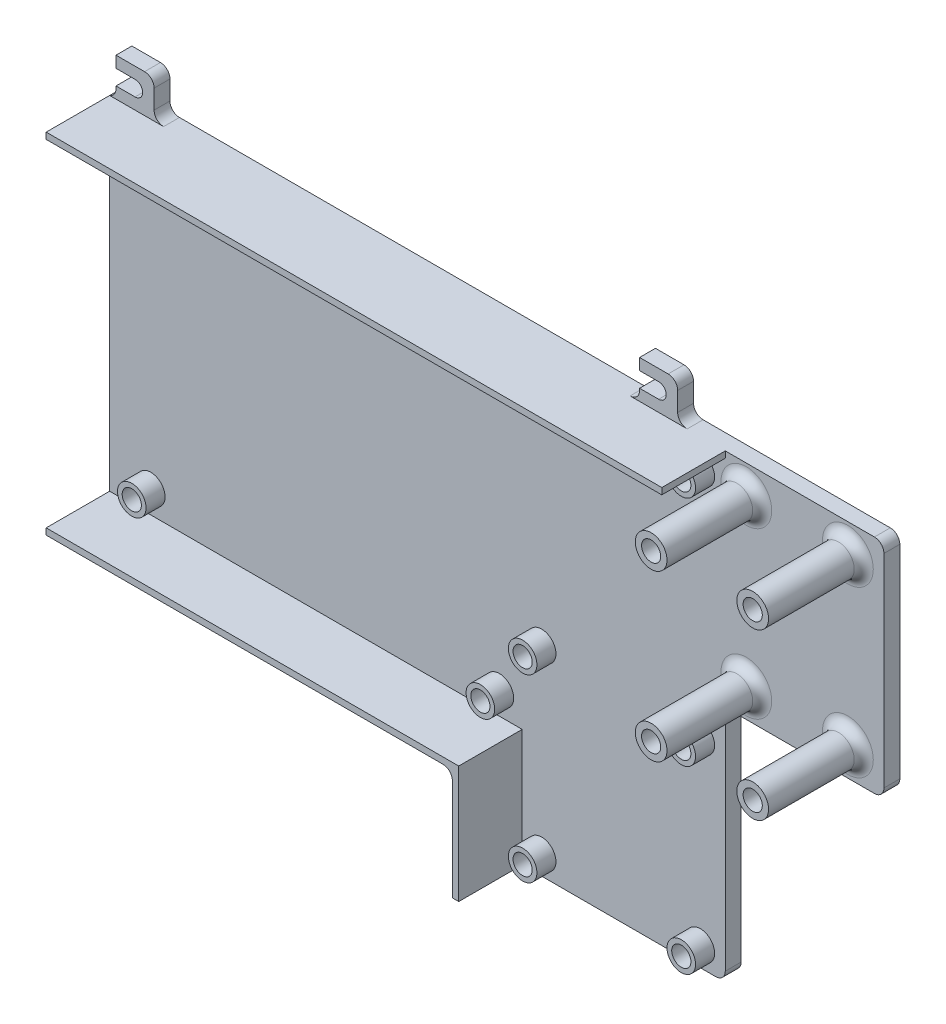
SolidWorks part; units mm, degrees
material "ABS"
ref_plane "X-Y Datum" through (0, 0, 0) normal (0, 0, 1) x (1, 0, 0)
ref_plane "X-Z Datum" through (0, 0, 0) normal (0, 1, 0) x (1, 0, 0)
ref_plane "Y-Z Datum" through (0, 0, 0) normal (1, 0, 0) x (0, 0, -1)
sketch "Sketch1" plane through (0, 0, 0) normal (0, 0, 1) x (1, 0, 0)
  line L1 (-167.3248, 270.3744) -> (-39.3248, 270.3744)
  line L2 (-167.3248, 270.3744) -> (-167.3248, 160.3744)
  line L3 (-167.3248, 160.3744) -> (-39.3248, 160.3744)
  line L4 (-39.3248, 270.3744) -> (-39.3248, 160.3744)
  line L5 (-39.3248, 270.3744) -> (26.6752, 270.3744)
  line L6 (-39.3248, 270.3744) -> (-39.3248, 125.3744)
  line L7 (-39.3248, 125.3744) -> (26.6752, 125.3744)
  line L8 (26.6752, 270.3744) -> (26.6752, 125.3744)
  line L10 (26.6752, 125.3744) -> (26.6752, 195.3744)
  line L13 (26.6752, 270.3744) -> (76.6752, 270.3744)
  line L14 (26.6752, 270.3744) -> (26.6752, 200.3744)
  line L15 (26.6752, 200.3744) -> (76.6752, 200.3744)
  line L16 (76.6752, 270.3744) -> (76.6752, 200.3744)
  dimension "D1" = 110
  dimension "D2" = 128
  dimension "D3" = 66
  dimension "D4" = 145
  dimension "D7" = 70
  dimension "D8" = 50
extrude "Boss-Extrude1" add sketch "Sketch1" along normal blind 5 contours L4 L1 L2 L3 | L8 L5 L4 L6 L7 | L8 region at (-103.3248, 215.3744, 0) region at (-6.3248, 197.8744, 0) region at (51.6752, 235.3744, 0)
sketch "Sketch2" plane through (0, 0, 5) normal (0, 0, 1) x (1, 0, 0)
  circle A0 centre (-44.4998, 262.4914) radius 3.025
  circle A1 centre (-154.3548, 262.4914) radius 3.025
  circle A2 centre (-154.3548, 262.4914) radius 4.5
  circle A3 centre (-44.4998, 262.4914) radius 4.5
  circle A4 centre (-44.4998, 169.5274) radius 3.025
  circle A5 centre (-44.4998, 169.5274) radius 4.5
  circle A6 centre (-154.3548, 169.5274) radius 4.5
  circle A7 centre (-154.3548, 169.5274) radius 3.025
  circle A8 centre (-31.1818, 131.5554) radius 4.5
  circle A9 centre (-31.1818, 131.5554) radius 3.025
  circle A10 centre (18.8182, 131.5554) radius 3.025
  circle A11 centre (18.8182, 131.5554) radius 4.5
  circle A12 centre (18.8182, 188.3054) radius 3.025
  circle A13 centre (18.8182, 188.3054) radius 4.5
  circle A14 centre (-31.1818, 188.3054) radius 4.5
  circle A15 centre (-31.1818, 188.3054) radius 3.025
  circle A16 centre (-31.1818, 261.5554) radius 3.025
  circle A17 centre (-31.1818, 261.5554) radius 4.5
  circle A18 centre (18.8182, 261.5554) radius 4.5
  circle A19 centre (18.8182, 261.5554) radius 3.025
  point P0 (-154.3548, 262.4914)
  point P1 (-44.4998, 262.4914)
  point P3 (-44.4998, 169.5274)
  point P5 (-154.3548, 169.5274)
  point P7 (18.8182, 261.5554)
  point P9 (-31.1818, 261.5554)
  point P11 (-31.1818, 188.3054)
  point P13 (-31.1818, 131.5554)
  point P15 (18.8182, 131.5554)
  point P17 (18.8182, 188.3054)
  dimension "D1" = 6.05
  dimension "D2" = 9
extrude "Boss-Extrude2" add sketch "Sketch2" along normal blind 6
sketch "Sketch3" plane through (0, 0, 5) normal (0, 0, 1) x (1, 0, 0)
  line L0 (26.6752, 200.3744) -> (26.6752, 125.3744) construction
  line L1 (-167.3248, 270.3744) -> (26.6752, 270.3744)
  line L2 (-167.3248, 270.3744) -> (-167.3248, 268.3744)
  line L3 (-167.3248, 268.3744) -> (26.6752, 268.3744)
  line L4 (26.6752, 270.3744) -> (26.6752, 268.3744)
  line L6 (-167.3248, 160.3744) -> (-39.3248, 160.3744)
  line L7 (-167.3248, 160.3744) -> (-167.3248, 162.3744)
  line L8 (-167.3248, 162.3744) -> (-39.3248, 162.3744)
  line L9 (-39.3248, 160.3744) -> (-39.3248, 162.3744)
  line L10 (-39.3248, 125.3744) -> (-37.3248, 125.3744)
  line L11 (-39.3248, 125.3744) -> (-39.3248, 162.3744)
  line L12 (-39.3248, 162.3744) -> (-37.3248, 162.3744)
  line L13 (-37.3248, 125.3744) -> (-37.3248, 162.3744)
  line M14 (-167.3248, 160.3744) -> (-39.3248, 160.3744)
  line M15 (-39.3248, 160.3744) -> (-39.3248, 125.3744)
  line M19 (26.6752, 125.3744) -> (26.6752, 200.3744)
  line M20 (76.6752, 270.3744) -> (-167.3248, 270.3744)
  line M21 (-167.3248, 270.3744) -> (-167.3248, 160.3744)
  dimension "D1" = 2
  dimension "D2" = 2
  dimension "D3" = 2
extrude "Boss-Extrude3" add sketch "Sketch3" along normal blind 20 contours L13 L12 L9 M15 | L9 L8 M14 M21 | L3 M21 M19 M20 region at (-103.3248, 161.3744, 5) region at (-70.3248, 269.3744, 5) region at (-38.3248, 143.8744, 5)
sketch "Sketch6" plane through (0, 0, 0) normal (0, 0, -1) x (-1, 0, 0)
  line L0 (167.3248, 160.3744) -> (39.3248, 160.3744) construction
  line L1 (137.3248, 160.3744) -> (125.3248, 160.3744)
  line L2 (137.3248, 160.3744) -> (137.3248, 148.3744)
  line L3 (137.3248, 148.3744) -> (125.3248, 148.3744)
  line L4 (125.3248, 160.3744) -> (125.3248, 148.3744)
  line L5 (-26.6752, 270.3744) -> (167.3248, 270.3744) construction
  line L6 (165.3248, 270.3744) -> (153.3248, 270.3744)
  line L7 (165.3248, 270.3744) -> (165.3248, 282.3744)
  line L8 (165.3248, 282.3744) -> (153.3248, 282.3744)
  line L9 (153.3248, 270.3744) -> (153.3248, 282.3744)
  line L11 (51.3248, 160.3744) -> (39.3248, 160.3744)
  line L12 (51.3248, 160.3744) -> (51.3248, 148.3744)
  line L13 (51.3248, 148.3744) -> (39.3248, 148.3744)
  line L14 (39.3248, 160.3744) -> (39.3248, 148.3744)
  line L15 (131.3248, 160.3744) -> (131.3248, 148.3744) construction
  line L16 (0.3248, 270.3744) -> (-11.6752, 270.3744)
  line L17 (0.3248, 270.3744) -> (0.3248, 282.3744)
  line L18 (0.3248, 282.3744) -> (-11.6752, 282.3744)
  line L19 (-11.6752, 270.3744) -> (-11.6752, 282.3744)
  line L20 (167.3248, 162.3744) -> (167.3248, 160.3744) construction
  line L21 (159.3248, 282.3744) -> (159.3248, 270.3744) construction
  line L22 (-5.6752, 282.3744) -> (-5.6752, 270.3744) construction
  line L23 (45.3248, 160.3744) -> (45.3248, 148.3744) construction
  line L24 (167.3248, 268.3744) -> (167.3248, 162.3744) construction
  line L27 (-26.6752, 200.3744) -> (-26.6752, 125.3744) construction
  line L29 (39.3248, 125.3744) -> (39.3248, 160.3744) construction
  circle A0 centre (131.3248, 154.3744) radius 2 construction
  circle A1 centre (45.3248, 154.3744) radius 2 construction
  circle A2 centre (-5.6752, 276.3744) radius 2 construction
  circle A3 centre (159.3248, 276.3744) radius 2 construction
  dimension "D1" = 4
  dimension "D2" = 12
  dimension "D3" = 12
  dimension "D4" = 30
  dimension "D5" = 2
  dimension "D6" = 15
extrude "Boss-Extrude5" add sketch "Sketch6" against normal blind 5
hole_wizard "M4 Clearance Hole1" positions "Sketch9" profile "Sketch8" hole size "M4" standard "ANSI Metric" end condition through all
sketch "Sketch9" plane through (0, 0, 5) normal (0, 0, 1) x (1, 0, 0)
  line L0 (-131.3248, 160.3744) -> (-131.3248, 148.3744) construction
  point P0 (-131.3248, 154.3744)
  point P4 (-159.3248, 276.3744)
  point P7 (5.6752, 276.3744)
  point P10 (-45.3248, 154.3744)
sketch "Sketch8" plane through (-131.3248, 154.3744, 5) normal (1, 0, 0) x (0, -1, 0)
  line L0 (0, 0) -> (0, 5)
  line L1 (0, 5) -> (2.4, 5)
  line L2 (2.4, 5) -> (2.4, 0)
  line L5 (2.4, 0) -> (0, 0)
  line L11 (0, -6.35) -> (0, 107.95) construction
  dimension "Thru Hole Dia." = 4.8
  dimension "Thru Hole Depth" = 5
sketch "Sketch10" plane through (0, 0, 5) normal (0, 0, 1) x (1, 0, 0)
  line L0 (-159.3248, 278.7744) -> (-165.3248, 278.7744)
  line L1 (-159.3248, 282.3744) -> (-159.3248, 270.3744) construction
  line L2 (-165.3248, 270.3744) -> (-165.3248, 282.3744) construction
  line L3 (-159.3248, 273.9744) -> (-165.3248, 273.9744)
  line L4 (-131.3248, 156.7744) -> (-137.3248, 156.7744)
  line L5 (-131.3248, 160.3744) -> (-131.3248, 148.3744) construction
  line L6 (-137.3248, 160.3744) -> (-137.3248, 148.3744) construction
  line L7 (-131.3248, 151.9744) -> (-137.3248, 151.9744)
  line L8 (-45.3248, 156.7744) -> (-51.3248, 156.7744)
  line L9 (-45.3248, 160.3744) -> (-45.3248, 148.3744) construction
  line L10 (-51.3248, 160.3744) -> (-51.3248, 148.3744) construction
  line L11 (-45.3248, 151.9744) -> (-51.3248, 151.9744)
  line L12 (5.6752, 278.7744) -> (-0.3248, 278.7744)
  line L13 (5.6752, 282.3744) -> (5.6752, 270.3744) construction
  line L14 (-0.3248, 270.3744) -> (-0.3248, 282.3744) construction
  line L15 (5.6752, 273.9744) -> (-0.3248, 273.9744)
  line L16 (-51.3248, 148.3744) -> (-51.3248, 160.3744) construction
  line L17 (-51.3248, 148.3744) -> (-51.3248, 160.3744)
  line L20 (-137.3248, 160.3744) -> (-137.3248, 148.3744)
  line L21 (-137.3248, 148.3744) -> (-125.3248, 148.3744)
  line L22 (-125.3248, 148.3744) -> (-125.3248, 160.3744)
  line L23 (-125.3248, 160.3744) -> (-137.3248, 160.3744)
  line L24 (-137.3248, 160.3744) -> (-137.3248, 148.3744)
  line L25 (-137.3248, 148.3744) -> (-125.3248, 148.3744)
  line L26 (-125.3248, 148.3744) -> (-125.3248, 160.3744)
  line L27 (-125.3248, 160.3744) -> (-137.3248, 160.3744)
  line L28 (-0.3248, 282.3744) -> (-0.3248, 270.3744)
  line L29 (-0.3248, 270.3744) -> (11.6752, 270.3744)
  line L30 (26.6752, 125.3744) -> (26.6752, 200.3744)
  line L34 (26.6752, 268.3744) -> (-167.3248, 268.3744)
  line L35 (-167.3248, 268.3744) -> (-167.3248, 162.3744)
  line L36 (-167.3248, 162.3744) -> (-37.3248, 162.3744)
  line L37 (-37.3248, 162.3744) -> (-37.3248, 125.3744)
  line L38 (26.6752, 200.3744) -> (76.6752, 200.3744)
  line L48 (26.6752, 268.3744) -> (-167.3248, 268.3744)
  line L49 (-167.3248, 268.3744) -> (-167.3248, 162.3744)
  line L50 (-167.3248, 162.3744) -> (-37.3248, 162.3744)
  line L51 (-37.3248, 162.3744) -> (-37.3248, 125.3744)
  line L58 (11.6752, 270.3744) -> (11.6752, 282.3744)
  line L59 (11.6752, 282.3744) -> (-0.3248, 282.3744)
  line L60 (-0.3248, 282.3744) -> (-0.3248, 270.3744)
  line L61 (-0.3248, 270.3744) -> (11.6752, 270.3744)
  line L62 (11.6752, 270.3744) -> (11.6752, 282.3744)
  line L63 (11.6752, 282.3744) -> (-0.3248, 282.3744)
  line L64 (-165.3248, 282.3744) -> (-165.3248, 270.3744)
  line L65 (-165.3248, 270.3744) -> (-153.3248, 270.3744)
  line L66 (-153.3248, 270.3744) -> (-153.3248, 282.3744)
  line L67 (-153.3248, 282.3744) -> (-165.3248, 282.3744)
  line L68 (-165.3248, 282.3744) -> (-165.3248, 270.3744)
  line L69 (-165.3248, 270.3744) -> (-153.3248, 270.3744)
  line L70 (-153.3248, 270.3744) -> (-153.3248, 282.3744)
  line L71 (-153.3248, 282.3744) -> (-165.3248, 282.3744)
  line L80 (26.6752, 200.3744) -> (76.6752, 200.3744)
  line L82 (76.6752, 200.3744) -> (76.6752, 270.3744)
  line L84 (76.6752, 200.3744) -> (76.6752, 270.3744)
  line L85 (76.6752, 270.3744) -> (26.6752, 270.3744)
  line L86 (76.6752, 270.3744) -> (26.6752, 270.3744)
  line L87 (26.6752, 270.3744) -> (26.6752, 268.3744)
  line L89 (-37.3248, 125.3744) -> (26.6752, 125.3744)
  line L90 (-37.3248, 125.3744) -> (26.6752, 125.3744)
  line L94 (26.6752, 270.3744) -> (26.6752, 268.3744)
  line L95 (26.6752, 125.3744) -> (26.6752, 200.3744)
  circle A0 centre (-159.3248, 276.3744) radius 2.4 construction
  circle A1 centre (-131.3248, 154.3744) radius 2.4 construction
  circle A2 centre (-45.3248, 154.3744) radius 2.4 construction
  circle A3 centre (5.6752, 276.3744) radius 2.4 construction
  circle A4 centre (-159.3248, 276.3744) radius 2.4
  circle A5 centre (5.6752, 276.3744) radius 2.4
  circle A10 centre (-45.3248, 154.3744) radius 2.4
  circle A11 centre (-131.3248, 154.3744) radius 2.4
  circle M29 centre (-131.3248, 154.3744) radius 2.4
  line M30 (-137.3248, 160.3744) -> (-137.3248, 148.3744)
  dimension "D1" = 0
  dimension "D2" = 0
  dimension "D3" = 0
  dimension "D4" = 0
extrude "Cut-Extrude1" cut sketch "Sketch10" against normal through all contours L7 L4 M29 M30 | A4 L0 L68 L3 | A5 L12 L60 L15 | A10 L8 L11 region at (-163.2324, 276.3744, 5) region at (-135.2324, 154.3744, 5) region at (-49.2324, 154.3744, 5) region at (1.7676, 276.3744, 5)
fillet "Fillet2" radius 3 11 edges at (-153.3248, 282.3744, 2.5) (-153.3248, 270.3744, 2.5) (-165.3248, 270.3744, 2.5) (-0.3248, 270.3744, 2.5) (11.6752, 270.3744, 2.5) (11.6752, 282.3744, 2.5) (-125.3248, 148.3744, 2.5) (-137.3248, 160.3744, 2.5) (-125.3248, 160.3744, 2.5) (-51.3248, 160.3744, 2.5) (-39.3248, 148.3744, 2.5)
fillet "Fillet3" radius 3 5 edges at (-39.3248, 160.3744, 15) (26.6752, 200.3744, 2.5) (76.6752, 270.3744, 2.5) (76.6752, 200.3744, 2.5) (26.6752, 125.3744, 2.5)
sketch "Sketch11" plane through (0, 0, 5) normal (0, 0, 1) x (1, 0, 0)
  circle A0 centre (33.3182, 261.3744) radius 5
  circle A1 centre (65.3182, 261.3744) radius 3.025
  circle A2 centre (65.3182, 209.3744) radius 3.025
  circle A3 centre (33.3182, 209.3744) radius 3.025
  circle A4 centre (33.3182, 261.3744) radius 3.025
  circle A5 centre (65.3182, 261.3744) radius 5
  circle A6 centre (65.3182, 209.3744) radius 5
  circle A7 centre (33.3182, 209.3744) radius 5
  dimension "D1" = 6.05
  dimension "D2" = 10
extrude "Boss-Extrude6" add sketch "Sketch11" along normal blind 30
fillet "Fillet4" radius 3 4 edges at (70.3182, 261.3744, 5) (38.3182, 261.3744, 5) (38.3182, 209.3744, 5) (70.3182, 209.3744, 5)
equation "\"16mmm\"=20"
